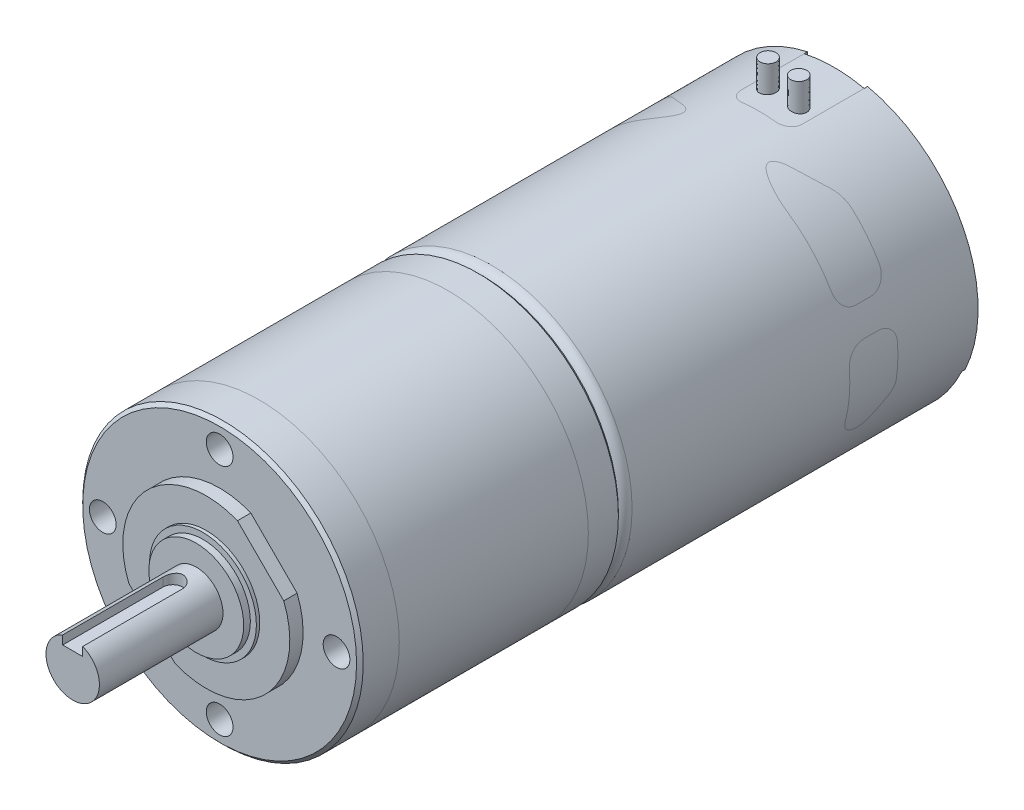
SolidWorks part; units mm, degrees
ref_plane "正面" through (0, 0, 0) normal (0, 0, 1) x (1, 0, 0)
ref_plane "平面" through (0, 0, 0) normal (0, 1, 0) x (1, 0, 0)
ref_plane "右側面" through (0, 0, 0) normal (1, 0, 0) x (0, 0, -1)
sketch "ｽｹｯﾁ1" plane through (0, 0, 0) normal (0, 0, 1) x (1, 0, 0)
  circle A0 centre (0, 0) radius 21.05
  dimension "D1" = 42.1
extrude "ﾎﾞｽ - 押し出し1" add sketch "ｽｹｯﾁ1" along normal blind 53.3
fillet "ﾌｨﾚｯﾄ1" radius 1.5 1 edges at (21.05, 0, 53.3)
sketch "ｽｹｯﾁ2" plane through (0, 0, 0) normal (0, 0, -1) x (-1, 0, 0)
  line L0 (-10.4652, -19.304) -> (-1.1004, -9.9393)
  line L1 (-4.1, 9.1209) -> (4.1, 9.1209)
  line L2 (-4.1, 9.1209) -> (-4.1, 21.05)
  line L3 (-4.1, 21.05) -> (4.1, 21.05)
  line L4 (4.1, 9.1209) -> (4.1, 21.05)
  line L5 (-10.4652, -19.304) -> (-19.304, -10.4652)
  line L6 (-1.1004, -9.9393) -> (-9.9393, -1.1004)
  line L7 (-19.304, -10.4652) -> (-9.9393, -1.1004)
  line L8 (10.4652, -19.304) -> (1.1004, -9.9393)
  line L9 (10.4652, -19.304) -> (19.304, -10.4652)
  line L10 (1.1004, -9.9393) -> (9.9393, -1.1004)
  line L11 (19.304, -10.4652) -> (9.9393, -1.1004)
  line L12 (0, 0) -> (0, -21.05) construction
  circle A1 centre (0, 0) radius 10
  circle A2 centre (0, 0) radius 19.85
  circle A3 centre (0, 0) radius 19.85
  circle A4 centre (0, 0) radius 21.05 construction
  arc A5 (-1.7678, -10.6066) -> (1.7678, -10.6066) centre (0, -12.3744) cw
  dimension "D2" = 20
  dimension "D5" = 2.5
  dimension "D3" = 8.2
  dimension "D4" = 12.5
  dimension "D1" = 1.2
extrude "ｶｯﾄ - 押し出し1" cut sketch "ｽｹｯﾁ2" against normal blind 0.5 contours L2 A3 L7 A1 | L11 A3 L4 A1 | L12 A1 L0 A3 | A1 L12 A3 L8 | L12 A5 A1 | A5 L12 A1 region at (3.1003, -15.7828, 0) region at (0.2642, -9.9447, 0) region at (12.4334, 6.2553, 0) region at (-3.1003, -15.7828, 0) region at (-0.2642, -9.9447, 0) region at (-12.4334, 6.2553, 0)
sketch "ｽｹｯﾁ3" plane through (0, 0, 0) normal (0, 0, -1) x (-1, 0, 0)
  circle A0 centre (0, 0) radius 7.5
  dimension "D1" = 15
extrude "ﾎﾞｽ - 押し出し2" add sketch "ｽｹｯﾁ3" along normal blind 4.2
sketch "ｽｹｯﾁ4" plane through (0, 0, -4.2) normal (0, 0, -1) x (-1, 0, 0)
  circle A0 centre (0, 0) radius 6.5
  dimension "D1" = 13
extrude "ｶｯﾄ - 押し出し2" cut sketch "ｽｹｯﾁ4" against normal blind 1
sketch "ｽｹｯﾁ5" plane through (0, 0, -3.2) normal (0, 0, -1) x (-1, 0, 0)
  circle A0 centre (0, 0) radius 2.5
  dimension "D1" = 5
extrude "ﾎﾞｽ - 押し出し3" add sketch "ｽｹｯﾁ5" along normal blind 1.3
fillet "ﾌｨﾚｯﾄ2" radius 0.75 1 edges at (-2.5, 0, -4.5)
fillet "ﾌｨﾚｯﾄ3" radius 2.5 4 edges at (9.9393, -1.1004, 0.25) (4.1, 9.1209, 0.25) (-4.1, 9.1209, 0.25) (-9.9393, -1.1004, 0.25)
fillet "ﾌｨﾚｯﾄ4" radius 0.5 13 edges at (5.3353, -14.1741, 0) (-5.3353, -14.1741, 0) (-14.2366, -5.3978, 0) (-10.1849, -1.0702, 0) (-8.7649, 4.8142, 0) (-4.4148, 9.4011, 0) (14.2366, -5.3978, 0) (10.1849, -1.0702, 0) (8.7649, 4.8142, 0) (4.4148, 9.4011, 0) (0, -9.8744, 0) (-4.1, 15.0188, 0) (4.1, 15.0188, 0)
sketch "ｽｹｯﾁ6" plane through (0, 0, 0) normal (0, 1, 0) x (1, 0, 0)
  line L0 (21.05, 0) -> (-21.05, 0) construction
  line L1 (-4.5, 0) -> (4.5, 0)
  line L2 (-4.5, 0) -> (-4.5, -9.8)
  line L3 (-2.5, -11.8) -> (2.5, -11.8)
  line L4 (4.5, 0) -> (4.5, -9.8)
  line L5 (-4.5, -6.9) -> (4.5, -6.9) construction
  line L6 (0, 0) -> (0, -11.8) construction
  line L7 (-3.5, 0) -> (-3.5, -11.8) construction
  circle A0 centre (-2.3, -8.1) radius 1.2
  circle A1 centre (2.3, -8.1) radius 1.2
  arc A2 (2.5, -11.8) -> (4.5, -9.8) centre (2.5, -9.8) ccw
  arc A3 (-4.5, -9.8) -> (-2.5, -11.8) centre (-2.5, -9.8) ccw
  point P21 (4.5, -11.8)
  point P24 (-4.5, -11.8)
  dimension "D4" = 2.4
  dimension "D6" = 2
  dimension "D1" = 11.8
  dimension "D2" = 9
  dimension "D3" = 6.9
  dimension "D5" = 1
split line "分割ﾗｲﾝ1"
sketch "ｽｹｯﾁ7" plane through (0, 0, 0) normal (0, 0, -1) x (-1, 0, 0)
  line L0 (0, 21.05) -> (0, -21.05) construction
  line L1 (0, 0) -> (-14.8846, -14.8846) construction
  line L2 (-4.5, 16.5) -> (4.5, 16.5)
  line L3 (-4.5, 16.5) -> (-4.5, 21.05)
  line L4 (-4.5, 21.05) -> (4.5, 21.05)
  line L5 (4.5, 16.5) -> (4.5, 21.05)
  line L6 (-4.5, 16.5) -> (4.5, 21.05) construction
  line L7 (-4.5, 21.05) -> (4.5, 16.5) construction
  line L8 (-6.2579, -16.5109) -> (-9.7581, -20.0111)
  line L9 (-6.2579, -16.5109) -> (-16.5109, -6.2579)
  line L10 (-9.7581, -20.0111) -> (-20.0111, -9.7581)
  line L11 (-16.5109, -6.2579) -> (-20.0111, -9.7581)
  line L12 (-6.2579, -16.5109) -> (-20.0111, -9.7581) construction
  line L13 (-9.7581, -20.0111) -> (-16.5109, -6.2579) construction
  line L14 (6.2579, -16.5109) -> (16.5109, -6.2579)
  line L15 (6.2579, -16.5109) -> (9.7581, -20.0111)
  line L16 (9.7581, -20.0111) -> (20.0111, -9.7581)
  line L17 (16.5109, -6.2579) -> (20.0111, -9.7581)
  arc A0 (4.5, 20.5634) -> (-4.5, 20.5634) centre (0, 0) ccw construction
  arc A1 (-4.5, 20.5634) -> (4.5, 20.5634) centre (0, 0) ccw construction
  circle A2 centre (0, 0) radius 7.5 construction
  point P8 (0, 18.775)
  point P16 (-5.3033, -5.3033)
  point P17 (-13.1345, -13.1345)
  point P25 (0, 7.5)
  dimension "D3" = 8.6
  dimension "D1" = 9
  dimension "D2" = 14.5
  dimension "D4" = 9
extrude "ｶｯﾄ - 押し出し3" cut sketch "ｽｹｯﾁ7" against normal up to surface (0.5 mm away) up to face at (0, -14.5181, 0.5)
sketch "ｽｹｯﾁ8" plane through (0, 0, 0) normal (0, 0, -1) x (-1, 0, 0)
  line L0 (0, 21.05) -> (0, -21.05) construction
  line L1 (-4.1012, -10.0409) -> (-6.364, -12.3037)
  line L2 (-4.1012, -8.6267) -> (-8.6267, -4.1012)
  line L3 (-7.7782, -12.3037) -> (-12.3037, -7.7782)
  line L4 (-10.0409, -4.1012) -> (-12.3037, -6.364)
  line L5 (-3.3941, -9.3338) -> (-13.0108, -7.0711) construction
  line L6 (-7.0711, -13.0108) -> (-9.3338, -3.3941) construction
  line L7 (18.1929, -7.9398) -> (19.1004, -8.8474) construction
  line L8 (4.1012, -8.6267) -> (8.6267, -4.1012)
  line L9 (4.1012, -10.0409) -> (6.364, -12.3037)
  line L10 (7.7782, -12.3037) -> (12.3037, -7.7782)
  line L11 (10.0409, -4.1012) -> (12.3037, -6.364)
  line L12 (-7.3186, -15.4503) -> (-15.4503, -7.3186) construction
  line L13 (-6.364, -6.364) -> (-10.0409, -10.0409) construction
  line L14 (8.8474, -19.1004) -> (7.9398, -18.1929) construction
  line L15 (6.965, -15.8038) -> (15.8038, -6.965) construction
  line L16 (-7.9398, -18.1929) -> (-8.8474, -19.1004) construction
  line L17 (-15.8038, -6.965) -> (-6.965, -15.8038) construction
  line L18 (-19.1004, -8.8474) -> (-18.1929, -7.9398) construction
  line L19 (4.1, 16.5) -> (-4.1, 16.5) construction
  line L20 (4.5, 20.5634) -> (4.5, 19.3332) construction
  line L21 (-4.5, 19.3332) -> (-4.5, 20.5634) construction
  line L22 (16.5109, -6.2579) -> (19.1004, -8.8474)
  line L23 (8.8474, -19.1004) -> (6.2579, -16.5109)
  line L24 (6.2579, -16.5109) -> (16.5109, -6.2579)
  line L25 (-6.2579, -16.5109) -> (-8.8474, -19.1004)
  line L26 (-16.5109, -6.2579) -> (-6.2579, -16.5109)
  line L27 (-19.1004, -8.8474) -> (-16.5109, -6.2579)
  line L28 (4.5, 16.5) -> (-4.5, 16.5)
  line L29 (4.5, 20.5634) -> (4.5, 16.5)
  line L30 (-4.5, 16.5) -> (-4.5, 20.5634)
  line L31 (-18.3653, 6.1) -> (-16.1153, 5.0103)
  line L32 (-18.3653, 6.1) -> (-15.75, 11.5)
  line L33 (-16.1153, 5.0103) -> (-13.5, 10.4103)
  line L34 (-15.75, 11.5) -> (-13.5, 10.4103)
  line L35 (15.75, 11.5) -> (13.5, 10.4103)
  line L36 (16.1153, 5.0103) -> (13.5, 10.4103)
  line L37 (18.3653, 6.1) -> (16.1153, 5.0103)
  line L38 (18.3653, 6.1) -> (15.75, 11.5)
  arc A0 (4.5, 20.5634) -> (-4.5, 20.5634) centre (0, 0) ccw construction
  arc A1 (-8.8474, -19.1004) -> (8.8474, -19.1004) centre (0, 0) ccw construction
  arc A2 (8.6267, -4.1012) -> (10.0409, -4.1012) centre (9.3338, -4.8083) cw
  arc A3 (12.3037, -7.7782) -> (12.3037, -6.364) centre (11.5966, -7.0711) ccw
  arc A4 (6.364, -12.3037) -> (7.7782, -12.3037) centre (7.0711, -11.5966) ccw
  arc A5 (4.1012, -8.6267) -> (4.1012, -10.0409) centre (4.8083, -9.3338) ccw
  arc A6 (-4.1012, -8.6267) -> (-4.1012, -10.0409) centre (-4.8083, -9.3338) cw
  arc A7 (-6.364, -12.3037) -> (-7.7782, -12.3037) centre (-7.0711, -11.5966) cw
  arc A8 (-12.3037, -7.7782) -> (-12.3037, -6.364) centre (-11.5966, -7.0711) cw
  arc A9 (-8.6267, -4.1012) -> (-10.0409, -4.1012) centre (-9.3338, -4.8083) ccw
  circle A10 centre (0, 0) radius 2.5 construction
  point P9 (-8.2024, -8.2024)
  point P50 (9.3338, -3.3941)
  point P53 (13.0108, -7.0711)
  point P56 (7.0711, -13.0108)
  point P59 (3.3941, -9.3338)
  dimension "D4" = 1
  dimension "D1" = 8.4
  dimension "D2" = 5.2
  dimension "D3" = 1.9
  dimension "D5" = 2.5
  dimension "D6" = 6
  dimension "D7" = 31.5
  dimension "D8" = 27
  dimension "D9" = 11.5
split line "分割ﾗｲﾝ2"
sketch "ｽｹｯﾁ9" plane through (0, 0, 53.3) normal (0, 0, 1) x (1, 0, 0)
  circle A0 centre (0, 0) radius 21
  dimension "D1" = 42
extrude "ﾎﾞｽ - 押し出し4" add sketch "ｽｹｯﾁ9" along normal blind 39.2
sketch "ｽｹｯﾁ10" plane through (0, 0, 92.5) normal (0, 0, 1) x (1, 0, 0)
  line L0 (4.6676, 11.5958) -> (11.5958, 4.6676)
  line L1 (-11.5958, -4.6676) -> (-4.6676, -11.5958)
  line L2 (0, 0) -> (0, 12.5) construction
  arc A0 (-4.6676, -11.5958) -> (11.5958, 4.6676) centre (0, 0) ccw
  arc A1 (4.6676, 11.5958) -> (-11.5958, -4.6676) centre (0, 0) ccw
  dimension "D1" = 25
  dimension "D2" = 23
  dimension "D3" = 45
extrude "ﾎﾞｽ - 押し出し5" add sketch "ｽｹｯﾁ10" along normal blind 2
sketch "ｽｹｯﾁ11" plane through (0, 0, 94.5) normal (0, 0, 1) x (1, 0, 0)
  circle A0 centre (0, 0) radius 8
  dimension "D1" = 16
extrude "ﾎﾞｽ - 押し出し6" add sketch "ｽｹｯﾁ11" along normal blind 0.5
sketch "ｽｹｯﾁ12" plane through (0, 0, 95) normal (0, 0, 1) x (1, 0, 0)
  circle A0 centre (0, 0) radius 7.1
  dimension "D1" = 14.2
extrude "ﾎﾞｽ - 押し出し7" add sketch "ｽｹｯﾁ12" along normal blind 1
sketch "ｽｹｯﾁ13" plane through (0, 0, 94.5) normal (0, 0, 1) x (1, 0, 0)
  circle A0 centre (0, 0) radius 4
  dimension "D1" = 8
extrude "ﾎﾞｽ - 押し出し8" add sketch "ｽｹｯﾁ13" along normal blind 20
ref_plane "平面2" through (0, 4, 0) normal (0, 1, 0) x (1, 0, 0)
sketch "ｽｹｯﾁ14" plane through (0, 4, 0) normal (0, 1, 0) x (1, 0, 0)
  line L0 (0, -114.5) -> (0, -99.5) construction
  line L1 (-4, -114.5) -> (4, -114.5) construction
  line L2 (-1.5, -114.5) -> (-1.5, -99.5)
  line L3 (1.5, -114.5) -> (1.5, -99.5)
  arc A0 (-1.5, -114.5) -> (1.5, -114.5) centre (0, -114.5) ccw
  arc A1 (1.5, -99.5) -> (-1.5, -99.5) centre (0, -99.5) ccw
  point P5 (0, -107)
  dimension "D2" = 1.5
  dimension "D1" = 15
extrude "ｶｯﾄ - 押し出し4" cut sketch "ｽｹｯﾁ14" against normal blind 1.6
sketch "ｽｹｯﾁ15" plane through (0, 0, 92.5) normal (0, 0, 1) x (1, 0, 0)
  circle A0 centre (0, 17.5) radius 2
  circle A1 centre (17.5, 0) radius 2
  circle A2 centre (0, -17.5) radius 2
  circle A3 centre (-17.5, 0) radius 2
  point P11 (0, 0)
  dimension "D1" = 4
  dimension "D3" = 35
  dimension "D2" = 4
extrude "ｶｯﾄ - 押し出し5" cut sketch "ｽｹｯﾁ15" against normal blind 6
sketch "ｽｹｯﾁ16" plane through (0, 0, 0) normal (0, 1, 0) x (1, 0, 0)
  line L0 (-21, -53.3) -> (-21, -92.5) construction
  line L1 (-21, -58.3) -> (21, -58.3)
  line L3 (-21, -86.6) -> (21, -86.6)
  line L5 (21, -92.5) -> (21, -53.3) construction
  line L6 (21, -53.3) -> (-21, -53.3) construction
  dimension "D1" = 28.3
  dimension "D2" = 5
split line "分割ﾗｲﾝ3"
sketch "ｽｹｯﾁ17" plane through (0, 0, 0) normal (1, 0, 0) x (0, 0, -1)
  line L0 (-19.2, 17.55) -> (-19.2, 10.55)
  line L1 (-16.7, 8.05) -> (-14.5, 8.05)
  line L2 (-12, 10.55) -> (-12, 15.55)
  line L3 (-12.8183, 17.3999) -> (-15.0183, 19.3999)
  line L4 (0, 6.15) -> (-53.3, 6.15) construction
  line L5 (0, -8.8474) -> (0, 20.5634) construction
  line L6 (-53.3, -21) -> (-53.3, 21) construction
  line L7 (-19.2, -5.25) -> (-19.2, 1.75)
  line L8 (-16.7, 4.25) -> (-14.5, 4.25)
  line L9 (-12, 1.75) -> (-12, -3.25)
  line L10 (-12.8183, -5.0999) -> (-15.0183, -7.0999)
  line L11 (-11.8, 21.05) -> (-51.8, 21.05) construction
  arc A0 (-19.2, 10.55) -> (-16.7, 8.05) centre (-16.7, 10.55) ccw
  arc A1 (-14.5, 8.05) -> (-12, 10.55) centre (-14.5, 10.55) ccw
  arc A2 (-12, 15.55) -> (-12.8183, 17.3999) centre (-14.5, 15.55) ccw
  arc A3 (-19.2, 17.55) -> (-15.0183, 19.3999) centre (-16.7, 17.55) cw
  arc A4 (-19.2, 1.75) -> (-16.7, 4.25) centre (-16.7, 1.75) cw
  arc A5 (-14.5, 4.25) -> (-12, 1.75) centre (-14.5, 1.75) cw
  arc A6 (-12, -3.25) -> (-12.8183, -5.0999) centre (-14.5, -3.25) cw
  arc A7 (-19.2, -5.25) -> (-15.0183, -7.0999) centre (-16.7, -5.25) ccw
  dimension "D1" = 2.5
  dimension "D3" = 7
  dimension "D7" = 3.5
  dimension "D2" = 3.8
  dimension "D4" = 5
  dimension "D5" = 2.2
  dimension "D6" = 12
split line "分割ﾗｲﾝ4"
sketch "ｽｹｯﾁ18" plane through (0, 0, 0) normal (0, 1, 0) x (1, 0, 0)
  line L0 (8.8474, 0) -> (-8.8474, 0) construction
  line L1 (-2, -12) -> (2, -12)
  line L2 (-4, -14) -> (-4, -17.3)
  line L3 (-2, -19.3) -> (2, -19.3)
  line L4 (4, -14) -> (4, -17.3)
  line L5 (-4, -12) -> (4, -19.3) construction
  line L6 (-4, -19.3) -> (4, -12) construction
  arc A0 (-2, -12) -> (-4, -14) centre (-2, -14) ccw
  arc A1 (2, -12) -> (4, -14) centre (2, -14) cw
  arc A2 (2, -19.3) -> (4, -17.3) centre (2, -17.3) ccw
  arc A3 (-4, -17.3) -> (-2, -19.3) centre (-2, -17.3) ccw
  point P0 (0, -15.65)
  dimension "D4" = 2
  dimension "D1" = 8
  dimension "D2" = 7.3
  dimension "D3" = 12
split line "分割ﾗｲﾝ5"
chamfer "面取り1" distance 0.5 angle 45 2 edges at (21, 0, 53.3) (21, 0, 92.5)
sketch "ｽｹｯﾁ19" plane through (0, 0, 0) normal (0, 1, 0) x (1, 0, 0)
  spline S1 degree 3 poles (-2.4581, -9.3) (-2.1419, -9.3) (-1.9846, -9.2683) (-1.6958, -9.1485) (-1.5618, -9.059) (-1.3399, -8.8368) (-1.2508, -8.7035) (-1.1303, -8.4112) (-1.0995, -8.2547) (-1.1005, -7.9374) (-1.1325, -7.7809) (-1.2544, -7.4904) (-1.3447, -7.3571) (-1.5675, -7.1367) (-1.7022, -7.0479) (-1.9916, -6.9298) (-2.1493, -6.8993) (-2.4617, -6.9007) (-2.6179, -6.9323) (-2.9072, -7.0531) (-3.0386, -7.1411) (-3.2617, -7.365) (-3.3496, -7.4974) (-3.4695, -7.7884) (-3.5004, -7.9464) (-3.4996, -8.2603) (-3.4674, -8.4187) (-3.3467, -8.7074) (-3.2569, -8.8408) (-3.0353, -9.0611) (-2.9027, -9.1495) (-2.6129, -9.269) (-2.4581, -9.3) (-2.1419, -9.3) (-1.9846, -9.2683) knots -0.0625 -0.0625 0 0 0.0625 0.0625 0.125 0.125 0.1875 0.1875 0.25 0.25 0.3125 0.3125 0.375 0.375 0.4375 0.4375 0.5 0.5 0.5625 0.5625 0.625 0.625 0.6875 0.6875 0.75 0.75 0.8125 0.8125 0.875 0.875 0.9375 0.9375 1 1 1.0625 1.0625 1.125 only from (-2.3, -9.3) to (-2.3, -9.3)
  spline S2 degree 3 poles (-2.4581, -9.3) (-2.1419, -9.3) (-1.9846, -9.2683) (-1.6958, -9.1485) (-1.5618, -9.059) (-1.3399, -8.8368) (-1.2508, -8.7035) (-1.1303, -8.4112) (-1.0995, -8.2547) (-1.1005, -7.9374) (-1.1325, -7.7809) (-1.2544, -7.4904) (-1.3447, -7.3571) (-1.5675, -7.1367) (-1.7022, -7.0479) (-1.9916, -6.9298) (-2.1493, -6.8993) (-2.4617, -6.9007) (-2.6179, -6.9323) (-2.9072, -7.0531) (-3.0386, -7.1411) (-3.2617, -7.365) (-3.3496, -7.4974) (-3.4695, -7.7884) (-3.5004, -7.9464) (-3.4996, -8.2603) (-3.4674, -8.4187) (-3.3467, -8.7074) (-3.2569, -8.8408) (-3.0353, -9.0611) (-2.9027, -9.1495) (-2.6129, -9.269) (-2.4581, -9.3) (-2.1419, -9.3) (-1.9846, -9.2683) knots -0.0625 -0.0625 0 0 0.0625 0.0625 0.125 0.125 0.1875 0.1875 0.25 0.25 0.3125 0.3125 0.375 0.375 0.4375 0.4375 0.5 0.5 0.5625 0.5625 0.625 0.625 0.6875 0.6875 0.75 0.75 0.8125 0.8125 0.875 0.875 0.9375 0.9375 1 1 1.0625 1.0625 1.125 only from (-2.3, -9.3) to (-2.3, -9.3)
  spline S3 degree 3 poles (2.1419, -9.3) (2.4581, -9.3) (2.615, -9.2683) (2.9027, -9.1493) (3.0361, -9.0605) (3.2575, -8.84) (3.3469, -8.7073) (3.4683, -8.4163) (3.4998, -8.2599) (3.5001, -7.9424) (3.4688, -7.7859) (3.3484, -7.4953) (3.2591, -7.3622) (3.0385, -7.1414) (2.9052, -7.0522) (2.6179, -6.9324) (2.4608, -6.9006) (2.1485, -6.8994) (1.9914, -6.9297) (1.7002, -7.0488) (1.5675, -7.1363) (1.342, -7.3601) (1.2533, -7.4923) (1.1318, -7.7834) (1.1002, -7.9411) (1.0998, -8.2552) (1.1312, -8.4136) (1.251, -8.7034) (1.3406, -8.8377) (1.5625, -9.0595) (1.6958, -9.1487) (1.9865, -9.269) (2.1419, -9.3) (2.4581, -9.3) (2.615, -9.2683) knots -0.0625 -0.0625 0 0 0.0625 0.0625 0.125 0.125 0.1875 0.1875 0.25 0.25 0.3125 0.3125 0.375 0.375 0.4375 0.4375 0.5 0.5 0.5625 0.5625 0.625 0.625 0.6875 0.6875 0.75 0.75 0.8125 0.8125 0.875 0.875 0.9375 0.9375 1 1 1.0625 1.0625 1.125 only from (2.3, -9.3) to (2.3, -9.3)
  spline S4 degree 3 poles (2.1419, -9.3) (2.4581, -9.3) (2.615, -9.2683) (2.9027, -9.1493) (3.0361, -9.0605) (3.2575, -8.84) (3.3469, -8.7073) (3.4683, -8.4163) (3.4998, -8.2599) (3.5001, -7.9424) (3.4688, -7.7859) (3.3484, -7.4953) (3.2591, -7.3622) (3.0385, -7.1414) (2.9052, -7.0522) (2.6179, -6.9324) (2.4608, -6.9006) (2.1485, -6.8994) (1.9914, -6.9297) (1.7002, -7.0488) (1.5675, -7.1363) (1.342, -7.3601) (1.2533, -7.4923) (1.1318, -7.7834) (1.1002, -7.9411) (1.0998, -8.2552) (1.1312, -8.4136) (1.251, -8.7034) (1.3406, -8.8377) (1.5625, -9.0595) (1.6958, -9.1487) (1.9865, -9.269) (2.1419, -9.3) (2.4581, -9.3) (2.615, -9.2683) knots -0.0625 -0.0625 0 0 0.0625 0.0625 0.125 0.125 0.1875 0.1875 0.25 0.25 0.3125 0.3125 0.375 0.375 0.4375 0.4375 0.5 0.5 0.5625 0.5625 0.625 0.625 0.6875 0.6875 0.75 0.75 0.8125 0.8125 0.875 0.875 0.9375 0.9375 1 1 1.0625 1.0625 1.125 only from (2.3, -9.3) to (2.3, -9.3)
  dimension "D1" = 0
  dimension "D2" = 0
extrude "ﾎﾞｽ - 押し出し9" add sketch "ｽｹｯﾁ19" along normal blind 25
chamfer "面取り2" [suppressed] distance 0.2 angle 45
sketch "ｽｹｯﾁ21" [suppressed] plane through (0, 0, 0) normal (0, 1, 0) x (1, 0, 0)
  line L0 (-19.1004, -0.5) -> (-19.1004, -9)
  line L1 (-17.1004, -11) -> (-10.8474, -11)
  line L2 (-8.8474, -9) -> (-8.8474, -0.5)
  line L3 (-4.5, 0) -> (-21.05, 0) construction
  line L4 (0, 0) -> (0, -19.3) construction
  line L5 (2, -19.3) -> (-2, -19.3) construction
  line L6 (8.8474, -9) -> (8.8474, -0.5)
  line L7 (19.1004, -0.5) -> (19.1004, -9)
  line L8 (17.1004, -11) -> (10.8474, -11)
  arc A0 (19.1004, -9) -> (17.1004, -11) centre (17.1004, -9) cw
  arc A1 (8.8474, -9) -> (10.8474, -11) centre (10.8474, -9) ccw
  arc A2 (-10.8474, -11) -> (-8.8474, -9) centre (-10.8474, -9) ccw
  arc A3 (-19.1004, -9) -> (-17.1004, -11) centre (-17.1004, -9) ccw
  point P19 (19.1004, -11)
  point P22 (8.8474, -11)
  point P25 (-8.8474, -11)
  point P28 (-19.1004, -11)
  dimension "D2" = 2
  dimension "D1" = 11
split line "分割ﾗｲﾝ6" [suppressed]
